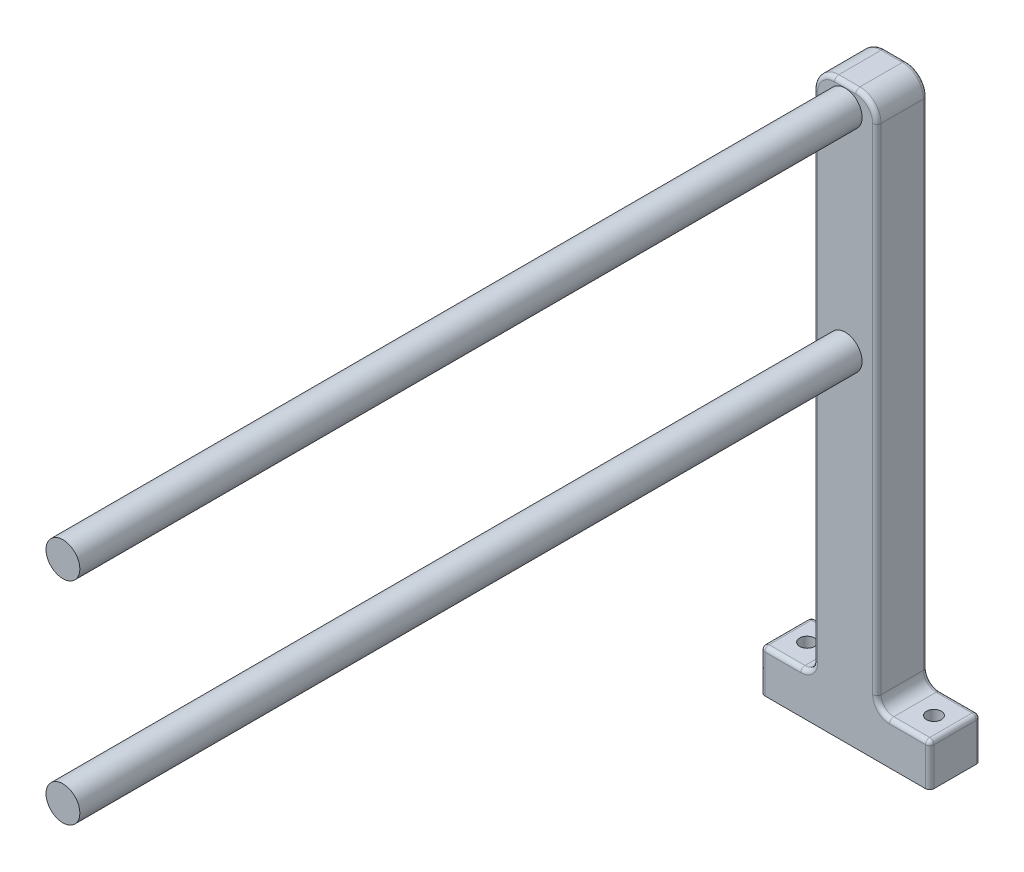
SolidWorks part; units mm, degrees
ref_plane "正面" through (0, 0, 0) normal (0, 0, 1) x (1, 0, 0)
ref_plane "平面" through (0, 0, 0) normal (0, 1, 0) x (1, 0, 0)
ref_plane "右側面" through (0, 0, 0) normal (1, 0, 0) x (0, 0, -1)
sketch "ｽｹｯﾁ1" plane through (0, 0, 0) normal (0, 0, 1) x (1, 0, 0)
  line L1 (7.5, -67.5) -> (-7.5, -67.5)
  line L2 (7.5, -67.5) -> (7.5, 67.5)
  line L3 (7.5, 67.5) -> (-7.5, 67.5)
  line L4 (-7.5, -67.5) -> (-7.5, 67.5)
  line L5 (7.5, -67.5) -> (-7.5, 67.5) construction
  line L6 (7.5, 67.5) -> (-7.5, -67.5) construction
  line L7 (-20, -57.5) -> (20, -57.5)
  line L8 (-20, -57.5) -> (-20, -67.5)
  line L9 (-20, -67.5) -> (20, -67.5)
  line L10 (20, -57.5) -> (20, -67.5)
  line L11 (-20, -57.5) -> (20, -67.5) construction
  line L12 (-20, -67.5) -> (20, -57.5) construction
  point P0 (0, 0)
  point P6 (0, -62.5)
  dimension "D1" = 15
  dimension "D2" = 135
  dimension "D3" = 10
  dimension "D4" = 40
  dimension "D5" = 0
  dimension "D6" = 0
extrude "ﾎﾞｽ - 押し出し1" add sketch "ｽｹｯﾁ1" along normal blind 12 contours L2 L3 L4 L1 | L7 L10 L9 L8
sketch "ｽｹｯﾁ2" plane through (0, 0, 12) normal (0, 0, 1) x (1, 0, 0)
  line L0 (20, -67.5) -> (-20, -67.5) construction
  circle A0 centre (0, 12.5) radius 4
  circle A1 centre (0, 62.5) radius 4
  dimension "D1" = 8
  dimension "D3" = 50
  dimension "D2" = 80
extrude "ﾎﾞｽ - 押し出し2" add sketch "ｽｹｯﾁ2" along normal blind 185
sketch "ｽｹｯﾁ3" plane through (0, -57.5, 0) normal (0, 1, 0) x (1, 0, 0)
  line L0 (20, -12) -> (20, 0) construction
  line L1 (-20, -12) -> (-20, 0) construction
  line L2 (7.5, 0) -> (20, 0) construction
  line L3 (-20, 0) -> (-7.5, 0) construction
  circle A0 centre (-15, -6) radius 1.75
  circle A1 centre (15, -6) radius 1.75
  dimension "D1" = 3.5
  dimension "D2" = 3.5
  dimension "D4" = 5
  dimension "D5" = 6
  dimension "D6" = 6
  dimension "D3" = 5
extrude "ｶｯﾄ - 押し出し1" cut sketch "ｽｹｯﾁ3" against normal through all
fillet "ﾌｨﾚｯﾄ1" radius 3 2 edges at (7.5, -57.5, 6) (-7.5, -57.5, 6)
fillet "ﾌｨﾚｯﾄ2" radius 5 2 edges at (7.5, 67.5, 6) (-7.5, 67.5, 6)
fillet "ﾌｨﾚｯﾄ3" radius 1 24 edges at (15.25, -57.5, 12) (8.3787, -56.6213, 12) (7.5, 4, 12) (6.0355, 66.0355, 12) (0, 67.5, 12) (-6.0355, 66.0355, 12) (-7.5, 4, 12) (-8.3787, -56.6213, 12) (15.25, -57.5, 0) (8.3787, -56.6213, 0) (7.5, 4, 0) (6.0355, 66.0355, 0) (0, 67.5, 0) (-6.0355, 66.0355, 0) (-7.5, 4, 0) (-8.3787, -56.6213, 0) (20, -62.5, 12) (20, -62.5, 0) (20, -57.5, 6) (-15.25, -57.5, 12) (-20, -62.5, 12) (-20, -62.5, 0) (-15.25, -57.5, 0) (-20, -57.5, 6)
